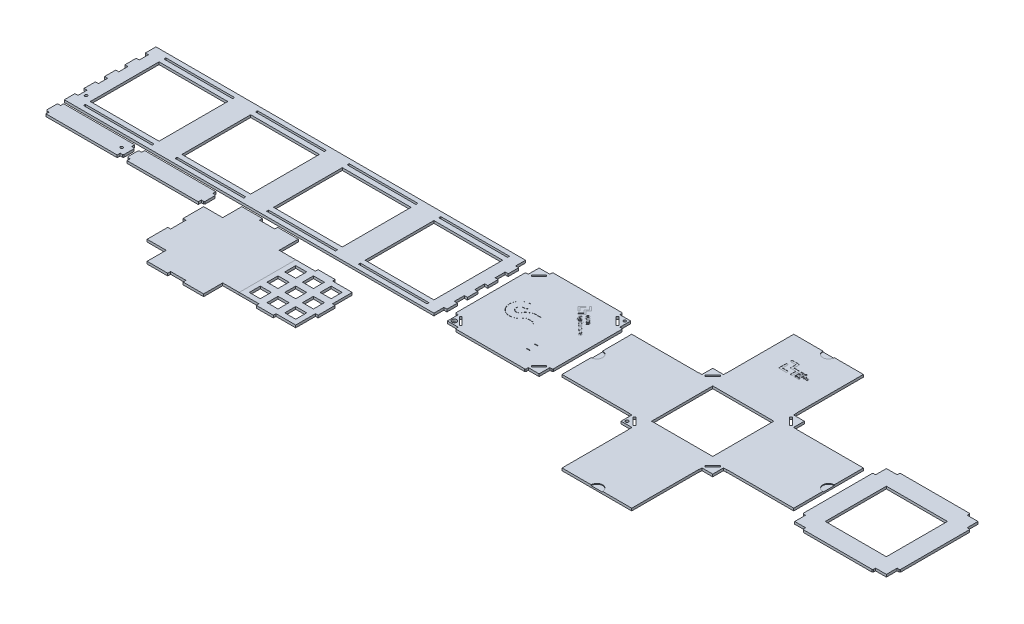
SolidWorks part; units mm, degrees
ref_plane "Front" through (0, 0, 0) normal (0, 0, 1) x (1, 0, 0)
ref_plane "Top" through (0, 0, 0) normal (0, 1, 0) x (1, 0, 0)
ref_plane "Right" through (0, 0, 0) normal (1, 0, 0) x (0, 0, -1)
sketch "Sketch1" plane through (0, 0, 0) normal (0, 1, 0) x (1, 0, 0)
  line L0 (0, 0) -> (228.6, 0) construction
  line L2 (-76.2, 76.2) -> (-76.2, -76.2) construction
  line L4 (76.2, 76.2) -> (76.2, -76.2) construction
  line L5 (-76.2, 76.2) -> (76.2, -76.2) construction
  line L6 (-76.2, -76.2) -> (76.2, 76.2) construction
  line L11 (76.2, 76.2) -> (228.6, 76.2)
  line L12 (76.2, 76.2) -> (76.2, -76.2) construction
  line L13 (76.2, -76.2) -> (228.6, -76.2)
  line L14 (228.6, 76.2) -> (228.6, -76.2) construction
  line L19 (-76.2, -76.2) -> (-228.6, -76.2)
  line L20 (-76.2, -76.2) -> (-76.2, 76.2) construction
  line L21 (-76.2, 76.2) -> (-228.6, 76.2)
  line L28 (76.2, -76.2) -> (-76.2, -76.2)
  line L34 (76.2, 76.2) -> (-76.2, 76.2)
  line L35 (-228.6, 76.2) -> (-228.6, -76.2) construction
  line L43 (-228.6, 76.2) -> (-381, 76.2)
  line L44 (-381, 76.2) -> (-381, -76.2) construction
  line L45 (-381, -76.2) -> (-228.6, -76.2)
  line L46 (228.6, 76.2) -> (228.6, 59.6392)
  line L47 (228.6, 59.6392) -> (233.68, 59.6392)
  line L48 (233.68, 59.6392) -> (233.68, 42.2402)
  line L49 (233.68, 42.2402) -> (228.6, 42.2402)
  line L50 (228.6, 42.2402) -> (228.6, 25.6794)
  line L51 (228.6, 25.6794) -> (233.68, 25.6794)
  line L63 (233.68, 25.6794) -> (233.68, 8.2804)
  line L64 (233.68, 8.2804) -> (228.6, 8.2804)
  line L65 (228.6, 8.2804) -> (228.6, -8.2804)
  line L66 (228.6, -8.2804) -> (233.68, -8.2804)
  line L67 (233.68, -8.2804) -> (233.68, -25.6794)
  line L68 (233.68, -25.6794) -> (228.6, -25.6794)
  line L69 (228.6, -25.6794) -> (228.6, -42.2402)
  line L70 (228.6, -42.2402) -> (233.68, -42.2402)
  line L71 (233.68, -42.2402) -> (233.68, -59.6392)
  line L72 (233.68, -59.6392) -> (228.6, -59.6392)
  line L73 (228.6, -59.6392) -> (228.6, -76.2)
  line L74 (-381, 76.2) -> (-386.08, 76.2)
  line L76 (-386.08, 58.5597) -> (-381, 58.5597)
  line L78 (-381, 43.3197) -> (-386.08, 43.3197)
  line L80 (-386.08, 24.5999) -> (-381, 24.5999)
  line L82 (-381, 9.3599) -> (-386.08, 9.3599)
  line L84 (-386.08, -9.3599) -> (-381, -9.3599)
  line L86 (-381, -24.5999) -> (-386.08, -24.5999)
  line L88 (-386.08, -43.3197) -> (-381, -43.3197)
  line L90 (-381, -58.5597) -> (-386.08, -58.5597)
  line L92 (-386.08, -76.2) -> (-381, -76.2)
  line L93 (233.68, 16.9799) -> (-381, 16.9799) construction
  line L94 (-381, 50.9397) -> (233.68, 50.9397) construction
  line L95 (-386.08, 76.2) -> (-386.08, 58.5597)
  line L96 (-386.08, 43.3197) -> (-386.08, 24.5999)
  line L97 (-381, 58.5597) -> (-381, 43.3197)
  line L98 (-381, 24.5999) -> (-381, 9.3599)
  line L99 (-381, -9.3599) -> (-381, -24.5999)
  line L100 (-381, -43.3197) -> (-381, -58.5597)
  line L101 (-381, -50.9397) -> (233.68, -50.9397) construction
  line L102 (-381, -16.9799) -> (233.68, -16.9799) construction
  line L103 (-386.08, 9.3599) -> (-386.08, -9.3599)
  line L104 (-386.08, -24.5999) -> (-386.08, -43.3197)
  line L105 (-386.08, -58.5597) -> (-386.08, -76.2)
  point P0 (0, 0)
  dimension "D1" = 152.4
  dimension "D3" = 5.08
  dimension "D5" = 15.24
  dimension "D4" = 17.399
  dimension "D2" = 152.4
extrude "Boss-Extrude1" add sketch "Sketch1" along normal blind 4.064
sketch "Sketch4" plane through (0, 4.064, 0) normal (0, 1, 0) x (1, 0, 0)
  line L0 (-228.6, 76.2) -> (-228.6, -76.2) construction
  line L1 (-228.6, 76.2) -> (-228.6, -76.2)
  line L2 (-76.2, 76.2) -> (-76.2, -76.2) construction
  line L3 (-76.2, 76.2) -> (-76.2, -76.2)
  line L4 (76.2, 76.2) -> (76.2, -76.2) construction
  line L5 (76.2, 76.2) -> (76.2, -76.2)
sketch "Sketch5" plane through (0, 4.064, 0) normal (0, 1, 0) x (1, 0, 0)
  line L0 (-381, -9.3599) -> (-381, 9.3599) construction
  line L1 (-228.6, 0) -> (-381, 0) construction
  line L2 (-228.6, 76.2) -> (-228.6, -76.2) construction
  line L3 (-228.6, 0) -> (-76.2, 0) construction
  line L4 (-76.2, 76.2) -> (-76.2, -76.2) construction
  line L5 (-76.2, 0) -> (76.2, 0) construction
  line L6 (76.2, 76.2) -> (76.2, -76.2) construction
  line L7 (76.2, 0) -> (228.6, 0) construction
  line L8 (228.6, -8.2804) -> (228.6, 8.2804) construction
  line L9 (-304.8, 0) -> (-304.8, -76.2) construction
  line L10 (-386.08, -76.2) -> (228.6, -76.2) construction
  line L11 (-152.4, 0) -> (-152.4, -76.2) construction
  line L12 (0, 0) -> (0, -76.2) construction
  line L13 (152.4, 0) -> (152.4, -76.2) construction
  line L14 (-247.65, -68.58) -> (-247.65, -76.2) construction
  line L15 (-361.95, -65.278) -> (-247.65, -65.278)
  line L16 (-361.95, -65.278) -> (-361.95, -68.58)
  line L17 (-361.95, -68.58) -> (-247.65, -68.58)
  line L18 (-247.65, -65.278) -> (-247.65, -68.58)
  line L19 (-361.95, -65.278) -> (-247.65, -68.58) construction
  line L20 (-361.95, -68.58) -> (-247.65, -65.278) construction
  line L21 (-209.55, -65.278) -> (-95.25, -65.278)
  line L22 (-209.55, -65.278) -> (-209.55, -68.58)
  line L23 (-209.55, -68.58) -> (-95.25, -68.58)
  line L24 (-95.25, -65.278) -> (-95.25, -68.58)
  line L25 (-209.55, -65.278) -> (-95.25, -68.58) construction
  line L26 (-209.55, -68.58) -> (-95.25, -65.278) construction
  line L27 (-57.15, -68.58) -> (57.15, -68.58)
  line L28 (-57.15, -68.58) -> (-57.15, -65.278)
  line L29 (-57.15, -65.278) -> (57.15, -65.278)
  line L30 (57.15, -68.58) -> (57.15, -65.278)
  line L31 (-57.15, -68.58) -> (57.15, -65.278) construction
  line L32 (-57.15, -65.278) -> (57.15, -68.58) construction
  line L33 (95.25, -68.58) -> (209.55, -68.58)
  line L34 (95.25, -68.58) -> (95.25, -65.278)
  line L35 (95.25, -65.278) -> (209.55, -65.278)
  line L36 (209.55, -68.58) -> (209.55, -65.278)
  line L37 (95.25, -68.58) -> (209.55, -65.278) construction
  line L38 (95.25, -65.278) -> (209.55, -68.58) construction
  line L39 (95.25, 65.278) -> (209.55, 68.58) construction
  line L40 (95.25, 68.58) -> (209.55, 65.278) construction
  line L41 (-57.15, 65.278) -> (57.15, 68.58) construction
  line L42 (-57.15, 68.58) -> (57.15, 65.278) construction
  line L43 (-209.55, 68.58) -> (-95.25, 65.278) construction
  line L44 (-209.55, 65.278) -> (-95.25, 68.58) construction
  line L45 (-361.95, 68.58) -> (-247.65, 65.278) construction
  line L46 (-361.95, 65.278) -> (-247.65, 68.58) construction
  line L47 (-247.65, 68.58) -> (-247.65, 76.2) construction
  line L48 (209.55, 68.58) -> (209.55, 65.278)
  line L49 (95.25, 65.278) -> (209.55, 65.278)
  line L50 (95.25, 68.58) -> (95.25, 65.278)
  line L51 (95.25, 68.58) -> (209.55, 68.58)
  line L52 (57.15, 68.58) -> (57.15, 65.278)
  line L53 (-57.15, 65.278) -> (57.15, 65.278)
  line L54 (-57.15, 68.58) -> (-57.15, 65.278)
  line L55 (-57.15, 68.58) -> (57.15, 68.58)
  line L56 (-95.25, 65.278) -> (-95.25, 68.58)
  line L57 (-209.55, 68.58) -> (-95.25, 68.58)
  line L58 (-209.55, 65.278) -> (-209.55, 68.58)
  line L59 (-209.55, 65.278) -> (-95.25, 65.278)
  line L60 (-247.65, 65.278) -> (-247.65, 68.58)
  line L61 (-361.95, 68.58) -> (-247.65, 68.58)
  line L62 (-361.95, 65.278) -> (-361.95, 68.58)
  line L63 (-361.95, 65.278) -> (-247.65, 65.278)
  line L65 (-361.95, 57.15) -> (-247.65, 57.15)
  line L66 (-361.95, 57.15) -> (-361.95, -57.15)
  line L67 (-361.95, -57.15) -> (-247.65, -57.15)
  line L68 (-247.65, 57.15) -> (-247.65, -57.15)
  line L69 (-361.95, 57.15) -> (-247.65, -57.15) construction
  line L70 (-361.95, -57.15) -> (-247.65, 57.15) construction
  line L71 (-209.55, 57.15) -> (-95.25, 57.15)
  line L72 (-209.55, 57.15) -> (-209.55, -57.15)
  line L73 (-209.55, -57.15) -> (-95.25, -57.15)
  line L74 (-95.25, 57.15) -> (-95.25, -57.15)
  line L75 (-209.55, 57.15) -> (-95.25, -57.15) construction
  line L76 (-209.55, -57.15) -> (-95.25, 57.15) construction
  line L77 (-57.15, 57.15) -> (57.15, 57.15)
  line L78 (-57.15, 57.15) -> (-57.15, -57.15)
  line L79 (-57.15, -57.15) -> (57.15, -57.15)
  line L80 (57.15, 57.15) -> (57.15, -57.15)
  line L81 (-57.15, 57.15) -> (57.15, -57.15) construction
  line L82 (-57.15, -57.15) -> (57.15, 57.15) construction
  line L83 (95.25, 57.15) -> (209.55, 57.15)
  line L84 (95.25, 57.15) -> (95.25, -57.15)
  line L85 (95.25, -57.15) -> (209.55, -57.15)
  line L86 (209.55, 57.15) -> (209.55, -57.15)
  line L87 (95.25, 57.15) -> (209.55, -57.15) construction
  line L88 (95.25, -57.15) -> (209.55, 57.15) construction
  circle A0 centre (-373.95, -52.15) radius 2.2225
  point P27 (-304.8, -66.929)
  point P32 (-152.4, -66.929)
  point P37 (0, -66.929)
  point P42 (152.4, -66.929)
  point P66 (152.4, 66.929)
  point P67 (0, 66.929)
  point P68 (-152.4, 66.929)
  point P69 (-304.8, 66.929)
  dimension "D5" = 4.445
  dimension "D1" = 7.62
  dimension "D3" = 114.3
  dimension "D6" = 12
  dimension "D7" = 5
  dimension "D8" = 19.05
  dimension "D2" = 3.302
  dimension "D4" = 8.128
extrude "Cut-Extrude2" cut sketch "Sketch5" against normal through all
sketch "Sketch6" plane through (0, 0, 0) normal (0, 1, 0) x (1, 0, 0)
  line L0 (0, 0) -> (327.279, 0) construction
  line L1 (327.279, 0) -> (327.279, 78.5495) construction
  line L2 (251.079, 76.2) -> (403.479, 76.2) construction
  line L3 (251.079, 76.2) -> (251.079, -76.2) construction
  line L4 (251.079, -76.2) -> (403.479, -76.2) construction
  line L5 (403.479, 76.2) -> (403.479, -76.2) construction
  line L6 (251.079, 76.2) -> (403.479, -76.2) construction
  line L7 (251.079, -76.2) -> (403.479, 76.2) construction
  line L8 (327.279, 0) -> (405.8285, 0) construction
  line L9 (327.279, 0) -> (327.279, -78.5495) construction
  line L10 (251.079, 58.2612) -> (251.079, 76.2)
  line L11 (269.0178, 80.899) -> (385.5403, 80.899)
  line L12 (269.0178, 80.899) -> (269.0178, 76.2)
  line L13 (269.0178, 76.2) -> (385.5403, 76.2) construction
  line L14 (385.5403, 80.899) -> (385.5403, 76.2)
  line L15 (269.0178, 80.899) -> (385.5403, 76.2) construction
  line L16 (269.0178, 76.2) -> (385.5403, 80.899) construction
  line L17 (408.178, -58.2612) -> (403.479, -58.2612)
  line L18 (408.178, -58.2612) -> (408.178, 58.2612)
  line L19 (408.178, 58.2612) -> (403.479, 58.2612)
  line L20 (403.479, -58.2612) -> (403.479, 58.2612) construction
  line L21 (408.178, -58.2612) -> (403.479, 58.2612) construction
  line L22 (408.178, 58.2612) -> (403.479, -58.2612) construction
  line L23 (269.0178, -80.899) -> (385.5403, -80.899)
  line L24 (269.0178, -80.899) -> (269.0178, -76.2)
  line L25 (269.0178, -76.2) -> (385.5403, -76.2) construction
  line L26 (385.5403, -80.899) -> (385.5403, -76.2)
  line L27 (269.0178, -80.899) -> (385.5403, -76.2) construction
  line L28 (269.0178, -76.2) -> (385.5403, -80.899) construction
  line L29 (246.38, 58.2612) -> (251.079, 58.2612)
  line L30 (246.38, 58.2612) -> (246.38, -58.2612)
  line L31 (246.38, -58.2612) -> (251.079, -58.2612)
  line L32 (251.079, 58.2612) -> (251.079, -58.2612) construction
  line L33 (246.38, 58.2612) -> (251.079, -58.2612) construction
  line L34 (246.38, -58.2612) -> (251.079, 58.2612) construction
  line L35 (251.079, 76.2) -> (269.0178, 76.2)
  line L36 (385.5403, 76.2) -> (403.479, 76.2)
  line L37 (403.479, 76.2) -> (403.479, 58.2612)
  line L38 (403.479, -58.2612) -> (403.479, -76.2)
  line L39 (403.479, -76.2) -> (385.5403, -76.2)
  line L40 (269.0178, -76.2) -> (251.079, -76.2)
  line L41 (251.079, -76.2) -> (251.079, -58.2612)
  line L42 (535.178, 58.2612) -> (535.178, -58.2612)
  line L43 (535.178, 58.2612) -> (539.877, 58.2612)
  line L44 (539.877, 58.2612) -> (539.877, 76.2)
  line L45 (539.877, 76.2) -> (557.8158, 76.2)
  line L46 (557.8158, 80.899) -> (557.8158, 76.2)
  line L47 (557.8158, 80.899) -> (674.3382, 80.899)
  line L48 (674.3382, 80.899) -> (674.3382, 76.2)
  line L49 (674.3382, 76.2) -> (692.277, 76.2)
  line L50 (692.277, 76.2) -> (692.277, 58.2612)
  line L51 (696.976, 58.2612) -> (692.277, 58.2612)
  line L52 (696.976, -58.2612) -> (696.976, 58.2612)
  line L53 (696.976, -58.2612) -> (692.277, -58.2612)
  line L54 (692.277, -58.2612) -> (692.277, -76.2)
  line L55 (692.277, -76.2) -> (674.3383, -76.2)
  line L56 (674.3383, -80.899) -> (674.3383, -76.2)
  line L57 (557.8158, -80.899) -> (674.3383, -80.899)
  line L58 (557.8158, -80.899) -> (557.8158, -76.2)
  line L59 (557.8158, -76.2) -> (539.877, -76.2)
  line L60 (539.877, -76.2) -> (539.877, -58.2612)
  line L61 (535.178, -58.2612) -> (539.877, -58.2612)
  line L62 (539.877, 76.2) -> (692.277, -76.2) construction
  line L63 (823.976, 58.2612) -> (823.976, -58.2612)
  line L64 (823.976, 58.2612) -> (828.675, 58.2612)
  line L65 (828.675, 58.2612) -> (828.675, 76.2)
  line L66 (828.675, 76.2) -> (846.6138, 76.2)
  line L67 (846.6138, 80.899) -> (846.6138, 76.2)
  line L68 (846.6138, 80.899) -> (963.1362, 80.899)
  line L69 (963.1362, 80.899) -> (963.1362, 76.2)
  line L70 (963.1362, 76.2) -> (981.075, 76.2)
  line L71 (981.075, 76.2) -> (981.075, 58.2612)
  line L72 (985.774, 58.2612) -> (981.075, 58.2612)
  line L73 (985.774, -58.2612) -> (985.774, 58.2612)
  line L74 (985.774, -58.2612) -> (981.075, -58.2612)
  line L75 (981.075, -58.2612) -> (981.075, -76.2)
  line L76 (981.075, -76.2) -> (963.1362, -76.2)
  line L77 (963.1362, -80.899) -> (963.1362, -76.2)
  line L78 (846.6138, -80.899) -> (963.1362, -80.899)
  line L79 (846.6138, -80.899) -> (846.6138, -76.2)
  line L80 (846.6138, -76.2) -> (828.675, -76.2)
  line L81 (828.675, -76.2) -> (828.675, -58.2612)
  line L82 (823.976, -58.2612) -> (828.675, -58.2612)
  line L83 (828.675, 76.2) -> (981.075, -76.2) construction
  line L84 (565.277, 50.8) -> (666.877, 50.8)
  line L85 (565.277, 50.8) -> (565.277, -50.8)
  line L86 (565.277, -50.8) -> (666.877, -50.8)
  line L87 (666.877, 50.8) -> (666.877, -50.8)
  line L88 (565.277, 50.8) -> (666.877, -50.8) construction
  line L89 (565.277, -50.8) -> (666.877, 50.8) construction
  line L90 (233.68, -25.6794) -> (233.68, -8.2804) construction
  line L91 (955.675, 50.8) -> (854.075, 50.8)
  line L92 (955.675, 50.8) -> (955.675, -50.8)
  line L93 (955.675, -50.8) -> (854.075, -50.8)
  line L94 (854.075, 50.8) -> (854.075, -50.8)
  line L95 (955.675, 50.8) -> (854.075, -50.8) construction
  line L96 (955.675, -50.8) -> (854.075, 50.8) construction
  line L97 (-76.2, -57.15) -> (76.2, -57.15) construction
  line L98 (-76.2, 76.2) -> (-76.2, -76.2) construction
  line L99 (76.2, 76.2) -> (76.2, -76.2) construction
  line L100 (76.2, -57.15) -> (228.6, -57.15) construction
  line L101 (228.6, -76.2) -> (228.6, -59.6392) construction
  line L102 (-57.15, -57.15) -> (57.15, -57.15) construction
  line L103 (95.25, 57.15) -> (209.55, 57.15) construction
  point P22 (248.7295, 0)
  point P67 (616.077, 0)
  point P72 (904.875, 0)
  dimension "D8" = 101.6
  dimension "D5" = 12.7
  dimension "D1" = 114.3
  dimension "D2" = 116.5225
  dimension "D4" = 127
  dimension "D3" = 4.699
  dimension "D6" = 3
extrude "Boss-Extrude2" add sketch "Sketch6" along normal up to surface (4.064 mm away) separate body up to face at (-152.4, 4.064, 0)
sketch "Sketch7" plane through (0, 0, 0) normal (0, 1, 0) x (1, 0, 0)
  line L0 (-361.95, 65.278) -> (-361.95, -53.086) construction
  line L1 (-381, -82.55) -> (-262.636, -82.55)
  line L2 (-381, -82.55) -> (-381, -87.63)
  line L3 (-381, -111.76) -> (-262.636, -111.76)
  line L4 (-262.636, -82.55) -> (-262.636, -87.63)
  line L5 (-381, -82.55) -> (-262.636, -111.76) construction
  line L6 (-381, -111.76) -> (-262.636, -82.55) construction
  line L7 (-361.95, 57.15) -> (-361.95, -57.15) construction
  line L8 (-361.95, -53.086) -> (-361.95, -57.15) construction
  line L9 (251.079, -58.2612) -> (251.079, -76.2) construction
  line L10 (251.079, -76.2) -> (269.0178, -76.2) construction
  line L12 (-381, -87.63) -> (-386.08, -87.63)
  line L13 (256.9951, -57.7116) -> (269.5674, -70.2839) construction
  line L14 (256.9951, -57.7116) -> (254.6602, -60.0464) construction
  line L15 (254.6602, -60.0464) -> (267.2326, -72.6188) construction
  line L16 (269.5674, -70.2839) -> (267.2326, -72.6188) construction
  line L17 (256.9951, -57.7116) -> (267.2326, -72.6188) construction
  line L18 (254.6602, -60.0464) -> (269.5674, -70.2839) construction
  line L19 (-386.08, -87.63) -> (-386.08, -106.68)
  line L20 (-386.08, -106.68) -> (-381, -106.68)
  line L22 (262.1138, -65.1652) -> (260.0484, -67.2306) construction
  line L23 (-381, -106.68) -> (-381, -111.76)
  line L24 (-262.636, -87.63) -> (-257.556, -87.63)
  line L25 (-257.556, -87.63) -> (-257.556, -106.68)
  line L26 (-257.556, -106.68) -> (-262.636, -106.68)
  line L27 (-262.636, -106.68) -> (-262.636, -111.76)
  line L28 (-386.08, -76.2) -> (228.6, -76.2) construction
  line L29 (-386.08, -58.5597) -> (-386.08, -76.2) construction
  line L30 (-246.126, -82.55) -> (-127.762, -82.55)
  line L31 (-246.126, -82.55) -> (-246.126, -87.63)
  line L32 (-246.126, -111.76) -> (-127.762, -111.76)
  line L33 (-127.762, -82.55) -> (-127.762, -87.63)
  line L34 (-246.126, -87.63) -> (-251.206, -87.63)
  line L35 (-251.206, -87.63) -> (-251.206, -106.68)
  line L36 (-251.206, -106.68) -> (-246.126, -106.68)
  line L37 (-246.126, -106.68) -> (-246.126, -111.76)
  line L38 (-127.762, -87.63) -> (-122.682, -87.63)
  line L39 (-122.682, -87.63) -> (-122.682, -106.68)
  line L40 (-122.682, -106.68) -> (-127.762, -106.68)
  line L41 (-127.762, -106.68) -> (-127.762, -111.76)
  line L42 (-246.126, -82.55) -> (-127.762, -111.76) construction
  line L43 (-246.126, -111.76) -> (-127.762, -82.55) construction
  line L44 (-361.95, 65.278) -> (-386.08, 65.278) construction
  line L45 (-386.08, 76.2) -> (-386.08, 58.5597) construction
  line L46 (251.079, -58.2612) -> (269.0178, -76.2) construction
  point P0 (-321.818, -97.155)
  point P14 (262.1138, -65.1652)
  point P38 (-186.944, -97.155)
  dimension "D1" = 29.21
  dimension "D4" = 19.05
  dimension "D5" = 17.78
  dimension "D7" = 6.35
  dimension "D9" = 6.35
  dimension "D10" = 1.27
  dimension "D3" = 3.302
  dimension "D6" = 5.08
  dimension "D2" = 4.064
extrude "PILLAR POSITION" add sketch "Sketch7" along normal up to surface (4.064 mm away) separate body up to face at (-152.4, 4.064, 0)
sketch "Sketch8" plane through (0, 4.064, 0) normal (0, 1, 0) x (1, 0, 0)
  line L0 (254.6602, -60.0464) -> (267.2326, -72.6188) construction
  line L1 (269.5674, -70.2839) -> (267.2326, -72.6188) construction
  line L2 (256.9951, -57.7116) -> (269.5674, -70.2839) construction
  line L3 (256.9951, -57.7116) -> (254.6602, -60.0464) construction
  line L4 (254.6602, -60.0464) -> (267.2326, -72.6188)
  line L5 (269.5674, -70.2839) -> (267.2326, -72.6188)
  line L6 (256.9951, -57.7116) -> (269.5674, -70.2839)
  line L7 (256.9951, -57.7116) -> (254.6602, -60.0464)
  line L8 (251.079, 76.2) -> (403.479, -76.2) construction
  line L9 (269.5674, 70.2839) -> (256.9951, 57.7116)
  line L10 (269.5674, 70.2839) -> (267.2326, 72.6188)
  line L11 (267.2326, 72.6188) -> (254.6602, 60.0464)
  line L12 (256.9951, 57.7116) -> (254.6602, 60.0464)
  line L13 (397.5629, 57.7116) -> (384.9906, 70.2839)
  line L14 (397.5629, 57.7116) -> (399.8978, 60.0464)
  line L15 (399.8978, 60.0464) -> (387.3254, 72.6188)
  line L16 (384.9906, 70.2839) -> (387.3254, 72.6188)
  line L17 (384.9906, -70.2839) -> (397.5629, -57.7116)
  line L18 (384.9906, -70.2839) -> (387.3254, -72.6188)
  line L19 (387.3254, -72.6188) -> (399.8978, -60.0464)
  line L20 (397.5629, -57.7116) -> (399.8978, -60.0464)
  line L21 (539.877, -58.2612) -> (557.8158, -76.2) construction
  line L22 (543.4582, -60.0464) -> (545.7931, -57.7116)
  line L23 (545.7931, -57.7116) -> (558.3654, -70.2839)
  line L24 (558.3654, -70.2839) -> (556.0306, -72.6188)
  line L25 (548.8464, -67.2306) -> (552.0793, -63.9977) construction
  line L26 (543.4582, -60.0464) -> (556.0306, -72.6188)
  line L27 (539.877, 76.2) -> (692.277, -76.2) construction
  line L28 (545.7931, 57.7116) -> (543.4582, 60.0464)
  line L29 (556.0306, 72.6188) -> (543.4582, 60.0464)
  line L30 (556.0306, 72.6188) -> (558.3654, 70.2839)
  line L31 (558.3654, 70.2839) -> (545.7931, 57.7116)
  line L32 (673.7886, 70.2839) -> (676.1234, 72.6188)
  line L33 (688.6958, 60.0464) -> (676.1234, 72.6188)
  line L34 (688.6958, 60.0464) -> (686.3609, 57.7116)
  line L35 (686.3609, 57.7116) -> (673.7886, 70.2839)
  line L36 (686.3609, -57.7116) -> (688.6958, -60.0464)
  line L37 (676.1234, -72.6188) -> (688.6958, -60.0464)
  line L38 (676.1234, -72.6188) -> (673.7886, -70.2839)
  line L39 (673.7886, -70.2839) -> (686.3609, -57.7116)
  line L40 (251.079, -58.2612) -> (269.0178, -76.2) construction
  line L41 (260.9464, -66.3326) -> (260.0484, -67.2306) construction
  line L42 (556.0306, -72.6188) -> (555.1326, -73.5168) construction
  circle A0 centre (327.279, 0) radius 20.7898 construction
  circle A1 centre (327.279, 0) radius 20.7898 construction
  circle A2 centre (327.279, 0) radius 20.7898 construction
  circle A3 centre (327.279, 0) radius 20.7898 construction
  circle A4 centre (616.077, 0) radius 71.842 construction
  point P28 (327.279, 0)
  point P58 (616.077, 0)
  dimension "D3" = 41.5796
  dimension "D1" = 4
  dimension "D2" = 4
extrude "Cut-Extrude3" cut sketch "Sketch8" against normal through all
sketch "Sketch10" plane through (0, 4.064, 0) normal (0, 1, 0) x (1, 0, 0)
  line L8 (-361.95, -53.086) -> (-247.65, -53.086)
  line L9 (-304.8, -53.086) -> (-304.8, -57.15) construction
  line L14 (-361.95, 57.15) -> (-361.95, -57.15) construction
  line L15 (-247.65, -57.15) -> (-247.65, 57.15) construction
  line L16 (-361.95, -57.15) -> (-247.65, -57.15) construction
  line L17 (-209.55, -53.086) -> (-95.25, -53.086)
  line L18 (-209.55, 57.15) -> (-209.55, -57.15) construction
  line L19 (-95.25, -57.15) -> (-95.25, 57.15) construction
  line L20 (-57.15, -53.086) -> (57.15, -53.086)
  line L21 (-57.15, 57.15) -> (-57.15, -57.15) construction
  line L22 (57.15, -57.15) -> (57.15, 57.15) construction
  line L23 (95.25, -53.086) -> (209.55, -53.086)
  line L24 (95.25, 57.15) -> (95.25, -57.15) construction
  line L25 (209.55, -57.15) -> (209.55, 57.15) construction
  line L27 (-361.95, 57.15) -> (-361.95, -53.086) construction
  dimension "D1" = 4.064
sketch "Sketch11" plane through (0, 0, 0) normal (0, 1, 0) x (1, 0, 0)
  line L0 (-209.55, -57.15) -> (-209.55, -65.278) construction
  line L5 (-84.582, -114.3) -> (9.398, -114.3) construction
  line L6 (-84.582, -114.3) -> (-84.582, -208.28) construction
  line L7 (-84.582, -208.28) -> (9.398, -208.28) construction
  line L8 (9.398, -114.3) -> (9.398, -208.28) construction
  line L9 (-84.582, -114.3) -> (9.398, -208.28) construction
  line L10 (-84.582, -208.28) -> (9.398, -114.3) construction
  line L11 (-84.582, -114.3) -> (-116.332, -114.3)
  line L12 (-116.332, -114.3) -> (-116.332, -208.28)
  line L13 (-116.332, -208.28) -> (-84.582, -208.28)
  line L14 (-84.582, -114.3) -> (-84.582, -82.55)
  line L15 (-84.582, -82.55) -> (9.398, -82.55)
  line L16 (9.398, -82.55) -> (9.398, -114.3)
  line L17 (9.398, -114.3) -> (36.83, -114.3)
  line L18 (36.83, -114.3) -> (36.83, -208.28)
  line L19 (36.83, -208.28) -> (9.398, -208.28)
  line L20 (9.398, -208.28) -> (9.398, -240.03)
  line L21 (9.398, -240.03) -> (-84.582, -240.03)
  line L22 (-84.582, -240.03) -> (-84.582, -208.28)
  line L23 (-386.08, -76.2) -> (228.6, -76.2) construction
  line L24 (-122.682, -106.68) -> (-122.682, -87.63) construction
  line L25 (-209.55, -57.15) -> (-95.25, -57.15) construction
  line L26 (565.277, -50.8) -> (666.877, -50.8) construction
  line L27 (209.55, -53.086) -> (209.55, -76.2) construction
  line L28 (-88.646, -237.49) -> (13.462, -237.49) construction
  line L29 (-37.592, -161.29) -> (-37.592, -237.49) construction
  line L30 (-88.646, -237.49) -> (-88.646, -240.03) construction
  line L31 (-88.646, -240.03) -> (-84.582, -240.03) construction
  line L32 (9.398, -240.03) -> (13.462, -240.03) construction
  line L33 (13.462, -240.03) -> (13.462, -237.49) construction
  point P0 (-37.592, -161.29)
  point P33 (-37.592, -237.49)
  dimension "D1" = 4.064
  dimension "D2" = 101.6
  dimension "D3" = 102.108
  dimension "D4" = 6.35
  dimension "D5" = 6.35
  dimension "D6" = 2.54
  dimension "D7" = 31.75
  dimension "D8" = 27.432
extrude "Boss-Extrude5" add sketch "Sketch11" along normal up to surface (4.064 mm away) separate body up to face at (-152.4, 4.064, 0)
sketch "Sketch12" plane through (0, 4.064, 0) normal (0, 1, 0) x (1, 0, 0)
  line L0 (-84.582, -114.3) -> (9.398, -114.3)
  line L1 (9.398, -114.3) -> (9.398, -208.28)
  line L2 (9.398, -208.28) -> (-84.582, -208.28)
  line L3 (-84.582, -114.3) -> (-84.582, -208.28)
sketch "Sketch14" plane through (0, 4.064, 0) normal (0, 1, 0) x (1, 0, 0)
  line L0 (-257.556, -97.155) -> (-269.7785, -97.155) construction
  line L1 (-257.556, -106.68) -> (-257.556, -87.63) construction
  circle A0 centre (-269.7785, -97.155) radius 2.2225
  circle A1 centre (-373.95, -52.15) radius 2.2225 construction
  dimension "D1" = 10
extrude "Cut-Extrude4" cut sketch "Sketch14" against normal through all
sketch "Sketch15" plane through (0, 4.064, 0) normal (0, 1, 0) x (1, 0, 0)
  line L0 (251.079, -76.2) -> (260.9464, -66.3326) construction
  line L1 (254.6602, -60.0464) -> (267.2326, -72.6188) construction
  line L2 (256.8592, -76.5158) -> (256.8592, -76.2) construction
  line L3 (251.079, -76.2) -> (269.0178, -76.2) construction
  line L4 (260.9464, -66.3326) -> (261.1697, -66.1093) construction
  line L5 (251.079, 76.2) -> (403.479, -76.2) construction
  line L6 (403.479, 76.2) -> (393.6116, 66.3326) construction
  line L7 (399.8978, 60.0464) -> (387.3254, 72.6188) construction
  line L8 (549.7444, -66.3326) -> (539.877, -76.2) construction
  line L9 (543.4582, -60.0464) -> (556.0306, -72.6188) construction
  circle A0 centre (256.8592, -70.4198) radius 3.95
  circle A1 centre (256.8592, -70.4198) radius 6.096 construction
  circle A2 centre (398.5453, 71.2663) radius 2.2225
  circle A3 centre (-269.7785, -97.155) radius 2.2225 construction
  circle A4 centre (544.8107, -71.2663) radius 2.413
  dimension "D1" = 7.9
  dimension "D2" = 12.192
  dimension "D3" = 4.826
extrude "Cut-Extrude5" cut sketch "Sketch15" against normal through all
sketch "Sketch16" [suppressed] plane through (0, 4.064, 0) normal (0, 1, 0) x (1, 0, 0)
  line L0 (565.277, 50.8) -> (565.277, -50.8) construction
  line L1 (568.452, 19.05) -> (481.6251, 19.05) construction
  line L2 (568.452, 38.1) -> (606.552, 38.1)
  line L3 (568.452, 38.1) -> (568.452, 0)
  line L4 (568.452, 0) -> (606.552, 0)
  line L6 (568.452, 38.1) -> (606.552, 0) construction
  line L7 (568.452, 0) -> (606.552, 38.1) construction
  line L8 (481.6251, 19.05) -> (587.502, 19.05) construction
  line L9 (606.552, 38.1) -> (606.552, 21.4244)
  line L10 (610.9668, 24.6016) -> (610.8822, 24.7481)
  line L11 (587.502, 38.1) -> (587.502, 0) construction
  line L12 (600.202, 24.13) -> (590.804, 24.13)
  line L13 (600.202, 13.97) -> (590.804, 13.97)
  line L14 (587.502, 24.13) -> (587.502, 13.97) construction
  line L15 (610.616, 24.13) -> (587.502, 24.13) construction
  line L16 (610.616, 13.97) -> (587.502, 13.97) construction
  line L17 (603.4053, 23.2628) -> (608.0662, 20.5397)
  line L18 (610.616, 19.05) -> (609.8932, 19.05) construction
  line L19 (610.616, 19.05) -> (587.502, 19.05) construction
  line L20 (625.8721, 19.05) -> (609.8932, 19.05) construction
  line L21 (600.202, 24.13) -> (600.202, 13.97) construction
  line L22 (606.552, -9.6369) -> (606.552, 0)
  line L23 (666.877, 50.8) -> (565.277, 50.8) construction
  line L24 (587.502, 27.432) -> (587.502, 27.94) construction
  line L25 (587.502, 10.668) -> (587.502, 10.16) construction
  line L26 (587.502, 27.432) -> (587.502, 10.668)
  arc A1 (611.0062, 17.4306) -> (614.2938, 22.6039) centre (614.172, 19.05) ccw
  arc A3 (614.4368, 30.7471) -> (610.8822, 24.7481) centre (614.3463, 26.7481) ccw
  arc A4 (610.9668, 24.6016) -> (614.2938, 22.6039) centre (614.4309, 26.6016) ccw
  arc A5 (603.4053, 23.2628) -> (600.202, 24.13) centre (600.202, 17.78) ccw
  arc A6 (605.1166, 11.6411) -> (600.202, 13.97) centre (600.202, 7.62) ccw
  arc A7 (611.0062, 17.4306) -> (608.0662, 20.5397) centre (604.2222, 13.9603) ccw
  arc A8 (590.804, 13.97) -> (587.502, 10.668) centre (590.804, 10.668) ccw
  arc A9 (587.502, 27.432) -> (590.804, 24.13) centre (590.804, 27.432) ccw
  arc A10 (605.1166, 11.6411) -> (614.4368, 30.7471) centre (614.172, 19.05) ccw
  point P4 (587.502, 19.05)
  point P28 (371.8905, 14.7821)
  dimension "D7" = 4
  dimension "D8" = 6.35
  dimension "D9" = 6.35
  dimension "D10" = 7.62
  dimension "D12" = 7.112
  dimension "D17" = 3.302
  dimension "D1" = 38.1
  dimension "D2" = 38.1
  dimension "D3" = 12.7
  dimension "D4" = 5.08
  dimension "D6" = 30
  dimension "D11" = 26.67
  dimension "D13" = 3.175
  dimension "D14" = 12.7
  dimension "D15" = 3.81
  dimension "D16" = 3.81
  dimension "D5" = 5.08
sketch "Sketch17" plane through (0, 4.064, 0) normal (0, 1, 0) x (1, 0, 0)
  line L1 (327.279, 80.899) -> (327.279, -80.899) construction
  line L12 (385.5403, 80.899) -> (269.0178, 80.899) construction
  line L13 (269.0178, -80.899) -> (385.5403, -80.899) construction
  line L30 (327.279, 10.16) -> (327.279, -10.16) construction
  line L31 (295.529, 0) -> (359.029, 0) construction
  line L32 (304.967, 2.1893) -> (310.047, 5.1321)
  line L34 (322.3603, -6.35) -> (314.579, -6.35)
  line L35 (314.579, 6.35) -> (322.3603, 6.35)
  arc A9 (310.047, 5.1321) -> (314.579, 6.35) centre (314.579, -2.6913) cw
  arc A10 (301.5552, -2.0019) -> (304.967, 2.1893) centre (308.7866, -4.4043) cw
  arc A11 (301.5552, -2.0019) -> (295.7963, 6.3444) centre (295.529, 0) cw
  arc A14 (310.4346, -8.7261) -> (296.256, 17.2567) centre (295.529, 0) cw
  arc A15 (310.4346, -8.7261) -> (314.579, -6.35) centre (314.579, -11.1524) cw
  arc A16 (322.3603, -6.35) -> (327.279, -10.16) centre (322.3603, -11.43) cw
  arc A17 (327.279, 10.16) -> (322.3603, 6.35) centre (322.3603, 11.43) cw
  arc A36 (296.256, 17.2567) -> (295.7963, 6.3444) centre (296.0261, 11.8005) cw
  point P43 (327.279, 0)
  point P64 (327.279, 0)
  dimension "D4" = 17.272
  dimension "D5" = 12.7
  dimension "D6" = 5.08
  dimension "D2" = 31.75
  dimension "D3" = 6.35
  dimension "D8" = 0.4971
  dimension "D9" = 7.62
  dimension "D7" = 20.32
  dimension "D10" = 5.08
  dimension "D11" = 12.7
  dimension "D12" = 30.084
extrude "Cut-Extrude-Thin1" cut sketch "Sketch17" against normal through all thin contours A16 L34 A15 A14 A36 A11 A10 L32 A9 L35 A17 thin type one direction wall 0.25
sketch "Sketch19" plane through (0, 4.064, 0) normal (0, 1, 0) x (1, 0, 0)
  line L0 (36.83, -114.3) -> (130.81, -208.28) construction
  line L1 (36.83, -114.3) -> (130.81, -114.3)
  line L2 (36.83, -114.3) -> (36.83, -208.28)
  line L3 (36.83, -208.28) -> (130.81, -208.28)
  line L4 (130.81, -114.3) -> (130.81, -208.28)
  line L6 (54.356, -131.826) -> (113.284, -131.826) construction
  line L7 (54.356, -131.826) -> (54.356, -190.754) construction
  line L8 (54.356, -190.754) -> (113.284, -190.754) construction
  line L9 (113.284, -131.826) -> (113.284, -190.754) construction
  line L10 (54.356, -131.826) -> (113.284, -190.754) construction
  line L11 (54.356, -190.754) -> (113.284, -131.826) construction
  line L12 (36.83, -114.3) -> (36.83, -208.28) construction
  line L13 (36.83, -114.3) -> (9.398, -114.3) construction
  line L14 (74.676, -122.682) -> (92.964, -122.682)
  line L15 (104.14, -122.682) -> (122.428, -122.682)
  line L16 (104.14, -122.682) -> (104.14, -140.97)
  line L17 (104.14, -140.97) -> (122.428, -140.97)
  line L18 (122.428, -122.682) -> (122.428, -140.97)
  line L19 (104.14, -122.682) -> (122.428, -140.97) construction
  line L20 (104.14, -140.97) -> (122.428, -122.682) construction
  line L21 (63.5, -122.682) -> (45.212, -122.682)
  line L22 (63.5, -122.682) -> (63.5, -140.97)
  line L23 (63.5, -140.97) -> (45.212, -140.97)
  line L24 (45.212, -122.682) -> (45.212, -140.97)
  line L25 (63.5, -122.682) -> (45.212, -140.97) construction
  line L26 (63.5, -140.97) -> (45.212, -122.682) construction
  line L27 (45.212, -181.61) -> (63.5, -181.61)
  line L28 (45.212, -181.61) -> (45.212, -199.898)
  line L29 (45.212, -199.898) -> (63.5, -199.898)
  line L30 (63.5, -181.61) -> (63.5, -199.898)
  line L31 (45.212, -181.61) -> (63.5, -199.898) construction
  line L32 (45.212, -199.898) -> (63.5, -181.61) construction
  line L33 (104.14, -181.61) -> (122.428, -181.61)
  line L34 (104.14, -181.61) -> (104.14, -199.898)
  line L35 (104.14, -199.898) -> (122.428, -199.898)
  line L36 (122.428, -181.61) -> (122.428, -199.898)
  line L37 (104.14, -181.61) -> (122.428, -199.898) construction
  line L38 (104.14, -199.898) -> (122.428, -181.61) construction
  line L39 (74.676, -122.682) -> (74.676, -140.97)
  line L40 (74.676, -140.97) -> (92.964, -140.97)
  line L41 (92.964, -122.682) -> (92.964, -140.97)
  line L42 (74.676, -122.682) -> (92.964, -140.97) construction
  line L43 (74.676, -140.97) -> (92.964, -122.682) construction
  line L44 (45.212, -152.146) -> (63.5, -152.146)
  line L45 (45.212, -152.146) -> (45.212, -170.434)
  line L46 (45.212, -170.434) -> (63.5, -170.434)
  line L47 (63.5, -152.146) -> (63.5, -170.434)
  line L48 (45.212, -152.146) -> (63.5, -170.434) construction
  line L49 (45.212, -170.434) -> (63.5, -152.146) construction
  line L50 (74.676, -181.61) -> (92.964, -181.61)
  line L51 (74.676, -181.61) -> (74.676, -199.898)
  line L52 (74.676, -199.898) -> (92.964, -199.898)
  line L53 (92.964, -181.61) -> (92.964, -199.898)
  line L54 (74.676, -181.61) -> (92.964, -199.898) construction
  line L55 (74.676, -199.898) -> (92.964, -181.61) construction
  line L56 (104.14, -152.146) -> (122.428, -152.146)
  line L57 (104.14, -152.146) -> (104.14, -170.434)
  line L58 (104.14, -170.434) -> (122.428, -170.434)
  line L59 (122.428, -152.146) -> (122.428, -170.434)
  line L60 (104.14, -152.146) -> (122.428, -170.434) construction
  line L61 (104.14, -170.434) -> (122.428, -152.146) construction
  line L62 (74.676, -152.146) -> (92.964, -152.146)
  line L63 (74.676, -152.146) -> (74.676, -170.434)
  line L64 (74.676, -170.434) -> (92.964, -170.434)
  line L65 (92.964, -152.146) -> (92.964, -170.434)
  line L66 (74.676, -152.146) -> (92.964, -170.434) construction
  line L67 (74.676, -170.434) -> (92.964, -152.146) construction
  point P4 (83.82, -161.29)
  point P31 (83.82, -131.826)
  point P36 (54.356, -161.29)
  point P41 (83.82, -190.754)
  point P46 (113.284, -161.29)
  point P51 (83.82, -161.29)
  point P58 (130.81, -114.3)
  dimension "D4" = 18.288
  dimension "D5" = 40.64
  dimension "D6" = 8.382
extrude "Boss-Extrude9" add sketch "Sketch19" against normal up to surface (4.064 mm away) separate body up to face at (-38.3117, 0, 161.29)
chamfer "Chamfer1" distance 1.27 angle 45 8 edges at (246.38, 2.032, -58.2612) (246.38, 2.032, 58.2612) (269.0178, 2.032, 80.899) (385.5403, 2.032, 80.899) (408.178, 2.032, 58.2612) (408.178, 2.032, -58.2612) (385.5403, 2.032, -80.899) (269.0178, 2.032, -80.899)
chamfer "Chamfer3" distance 1.25 angle 45 8 edges at (985.774, 2.032, -58.2612) (985.774, 2.032, 58.2612) (963.1362, 2.032, 80.899) (846.6138, 2.032, 80.899) (823.976, 2.032, 58.2612) (963.1362, 2.032, -80.899) (823.976, 2.032, -58.2612) (846.6138, 2.032, -80.899)
chamfer "Chamfer4" distance 1.25 angle 45 4 edges at (-257.556, 2.032, 106.68) (-257.556, 2.032, 87.63) (-386.08, 2.032, 106.68) (-386.08, 2.032, 87.63)
chamfer "Chamfer5" distance 1.25 angle 45 4 edges at (-122.682, 2.032, 87.63) (-122.682, 2.032, 106.68) (-251.206, 2.032, 106.68) (-251.206, 2.032, 87.63)
sketch "Sketch20" plane through (0, 4.064, 0) normal (0, 1, 0) x (1, 0, 0)
  line L0 (359.664, -36.83) -> (359.664, -50.038) construction
  line L1 (356.87, -36.449) -> (362.458, -36.449)
  line L2 (356.87, -36.449) -> (356.87, -37.211)
  line L3 (356.87, -37.211) -> (362.458, -37.211)
  line L4 (362.458, -36.449) -> (362.458, -37.211)
  line L5 (356.87, -36.449) -> (362.458, -37.211) construction
  line L6 (356.87, -37.211) -> (362.458, -36.449) construction
  line L7 (356.87, -49.657) -> (362.458, -49.657)
  line L8 (356.87, -49.657) -> (356.87, -50.419)
  line L9 (356.87, -50.419) -> (362.458, -50.419)
  line L10 (362.458, -49.657) -> (362.458, -50.419)
  line L11 (356.87, -49.657) -> (362.458, -50.419) construction
  line L12 (356.87, -50.419) -> (362.458, -49.657) construction
  line L13 (270.2878, -80.899) -> (384.2703, -80.899) construction
  line L14 (408.178, -56.9912) -> (408.178, 56.9912) construction
  point P0 (359.664, -36.83)
  point P5 (359.664, -50.038)
  dimension "D1" = 0.762
  dimension "D2" = 5.588
  dimension "D3" = 13.97
  dimension "D4" = 30.48
  dimension "D5" = 45.72
extrude "Cut-Extrude7" cut sketch "Sketch20" against normal through all
sketch "Sketch21" plane through (0, 4.064, 0) normal (0, 1, 0) x (1, 0, 0)
  line L0 (-37.592, -82.55) -> (-37.592, -240.03) construction
  line L1 (9.398, -82.55) -> (-84.582, -82.55) construction
  line L2 (-84.582, -240.03) -> (9.398, -240.03) construction
  line L3 (-116.332, -161.29) -> (36.83, -161.29) construction
  line L4 (-116.332, -114.3) -> (-116.332, -208.28) construction
  line L5 (36.83, -114.3) -> (36.83, -208.28) construction
  line L7 (-50.292, -82.55) -> (-24.892, -82.55)
  line L8 (-50.292, -82.55) -> (-50.292, -87.376)
  line L9 (-50.292, -87.376) -> (-24.892, -87.376)
  line L10 (-24.892, -82.55) -> (-24.892, -87.376)
  line L11 (-50.292, -82.55) -> (-24.892, -87.376) construction
  line L12 (-50.292, -87.376) -> (-24.892, -82.55) construction
  line L13 (-116.332, -148.59) -> (-111.506, -148.59)
  line L14 (-116.332, -148.59) -> (-116.332, -173.99)
  line L15 (-116.332, -173.99) -> (-111.506, -173.99)
  line L16 (-111.506, -148.59) -> (-111.506, -173.99)
  line L17 (-116.332, -148.59) -> (-111.506, -173.99) construction
  line L18 (-116.332, -173.99) -> (-111.506, -148.59) construction
  line L19 (-50.292, -235.204) -> (-24.892, -235.204)
  line L20 (-50.292, -235.204) -> (-50.292, -240.03)
  line L21 (-50.292, -240.03) -> (-24.892, -240.03)
  line L22 (-24.892, -235.204) -> (-24.892, -240.03)
  line L23 (-50.292, -235.204) -> (-24.892, -240.03) construction
  line L24 (-50.292, -240.03) -> (-24.892, -235.204) construction
  point P12 (-37.592, -84.963)
  point P17 (-113.919, -161.29)
  point P22 (-37.592, -237.617)
  dimension "D1" = 25.4
  dimension "D2" = 4.826
extrude "Cut-Extrude8" cut sketch "Sketch21" against normal through all
sketch "Sketch22" plane through (0, 0, 0) normal (0, -1, 0) x (-1, 0, 0)
  line L0 (-83.82, -114.3) -> (-83.82, -208.28) construction
  line L1 (-130.81, -114.3) -> (-36.83, -114.3) construction
  line L2 (-36.83, -208.28) -> (-130.81, -208.28) construction
  line L3 (-130.81, -161.29) -> (-83.82, -161.29) construction
  line L4 (-130.81, -208.28) -> (-130.81, -114.3) construction
  line L5 (-130.81, -114.3) -> (-36.83, -114.3) construction
  line L6 (-97.9805, -109.855) -> (-69.6595, -109.855)
  line L7 (-97.9805, -109.855) -> (-97.9805, -118.745)
  line L8 (-97.9805, -118.745) -> (-69.6595, -118.745)
  line L9 (-69.6595, -109.855) -> (-69.6595, -118.745)
  line L10 (-97.9805, -109.855) -> (-69.6595, -118.745) construction
  line L11 (-97.9805, -118.745) -> (-69.6595, -109.855) construction
  line L12 (-135.255, -147.1295) -> (-126.365, -147.1295)
  line L13 (-135.255, -147.1295) -> (-135.255, -175.4505)
  line L14 (-135.255, -175.4505) -> (-126.365, -175.4505)
  line L15 (-126.365, -147.1295) -> (-126.365, -175.4505)
  line L16 (-135.255, -147.1295) -> (-126.365, -175.4505) construction
  line L17 (-135.255, -175.4505) -> (-126.365, -147.1295) construction
  line L18 (-97.9805, -203.835) -> (-69.6595, -203.835)
  line L19 (-97.9805, -203.835) -> (-97.9805, -212.725)
  line L20 (-97.9805, -212.725) -> (-69.6595, -212.725)
  line L21 (-69.6595, -203.835) -> (-69.6595, -212.725)
  line L22 (-97.9805, -203.835) -> (-69.6595, -212.725) construction
  line L23 (-97.9805, -212.725) -> (-69.6595, -203.835) construction
  dimension "D2" = 28.321
  dimension "D1" = 4.445
extrude "Boss-Extrude10" add sketch "Sketch22" against normal up to surface (4.064 mm away) up to face at (83.82, 4.064, 161.29)
sketch "Sketch23" plane through (0, 4.064, 0) normal (0, 1, 0) x (1, 0, 0)
  line L0 (36.83, -208.28) -> (36.83, -114.3) construction
  line L1 (36.83, -208.28) -> (36.83, -114.3)
sketch "Sketch24" plane through (0, 4.064, 0) normal (0, 1, 0) x (1, 0, 0)
  line L0 (616.077, -80.899) -> (616.077, 80.899) construction
  line L1 (557.8158, -80.899) -> (674.3383, -80.899) construction
  line L2 (674.3382, 80.899) -> (557.8158, 80.899) construction
  line L3 (535.178, 0) -> (696.976, 0) construction
  line L4 (535.178, 58.2612) -> (535.178, -58.2612) construction
  line L5 (696.976, -58.2612) -> (696.976, 58.2612) construction
  line L7 (558.165, 80.899) -> (673.989, 80.899)
  line L8 (558.165, 80.899) -> (558.165, 192.659)
  line L9 (558.165, 192.659) -> (606.552, 192.659)
  line L10 (673.989, 80.899) -> (673.989, 192.659)
  line L11 (558.165, 80.899) -> (673.989, 192.659) construction
  line L12 (558.165, 192.659) -> (673.989, 80.899) construction
  line L13 (558.165, -80.899) -> (673.989, -80.899)
  line L14 (558.165, -80.899) -> (558.165, -192.659)
  line L15 (558.165, -192.659) -> (606.552, -192.659)
  line L16 (673.989, -80.899) -> (673.989, -192.659)
  line L17 (558.165, -80.899) -> (673.989, -192.659) construction
  line L18 (558.165, -192.659) -> (673.989, -80.899) construction
  line L19 (696.976, 57.912) -> (808.736, 57.912)
  line L20 (696.976, 57.912) -> (696.976, -57.912)
  line L21 (696.976, -57.912) -> (808.736, -57.912)
  line L22 (808.736, 57.912) -> (808.736, 9.525)
  line L23 (696.976, 57.912) -> (808.736, -57.912) construction
  line L24 (696.976, -57.912) -> (808.736, 57.912) construction
  line L25 (423.418, 57.912) -> (535.178, 57.912)
  line L26 (423.418, 57.912) -> (423.418, 9.525)
  line L27 (423.418, -57.912) -> (535.178, -57.912)
  line L28 (535.178, 57.912) -> (535.178, -57.912)
  line L29 (423.418, 57.912) -> (535.178, -57.912) construction
  line L30 (423.418, -57.912) -> (535.178, 57.912) construction
  line L31 (423.418, -9.525) -> (423.418, -57.912)
  line L32 (625.602, 192.659) -> (673.989, 192.659)
  line L33 (808.736, -9.525) -> (808.736, -57.912)
  line L34 (625.602, -192.659) -> (673.989, -192.659)
  arc A0 (423.418, -9.525) -> (423.418, 9.525) centre (423.418, 0) ccw
  arc A1 (625.602, -192.659) -> (606.552, -192.659) centre (616.077, -192.659) ccw
  arc A2 (606.552, 192.659) -> (625.602, 192.659) centre (616.077, 192.659) ccw
  arc A3 (808.736, 9.525) -> (808.736, -9.525) centre (808.736, 0) ccw
  point P12 (616.077, 136.779)
  point P17 (616.077, -136.779)
  point P22 (752.856, 0)
  point P27 (479.298, 0)
  dimension "D3" = 19.05
  dimension "D1" = 111.76
  dimension "D2" = 115.824
extrude "Boss-Extrude11" add sketch "Sketch24" against normal up to surface (4.064 mm away) up to face at (544.8107, 0, 73.6793)
sketch "Sketch25" plane through (0, 0, 0) normal (0, -1, 0) x (1, 0, 0)
  line L0 (625.602, -192.659) -> (606.552, -192.659)
  line L1 (423.418, 9.525) -> (423.418, -9.525)
  line L2 (625.602, 192.659) -> (606.552, 192.659)
  line L3 (808.736, 9.525) -> (808.736, -9.525)
  arc A0 (423.418, -9.525) -> (423.418, 9.525) centre (423.418, 0) ccw construction
  arc A1 (423.418, -9.525) -> (423.418, 9.525) centre (423.418, 0) ccw
  arc A2 (606.552, 192.659) -> (625.602, 192.659) centre (616.077, 192.659) ccw construction
  arc A3 (606.552, 192.659) -> (625.602, 192.659) centre (616.077, 192.659) ccw
  arc A4 (808.736, 9.525) -> (808.736, -9.525) centre (808.736, 0) ccw construction
  arc A5 (808.736, 9.525) -> (808.736, -9.525) centre (808.736, 0) ccw
  arc A6 (625.602, -192.659) -> (606.552, -192.659) centre (616.077, -192.659) ccw construction
  arc A7 (625.602, -192.659) -> (606.552, -192.659) centre (616.077, -192.659) ccw
extrude "Boss-Extrude12" add sketch "Sketch25" against normal offset from surface (2.794 mm away) 1.27 up to face at (544.8107, 4.064, 73.6793)
sketch "Sketch13" plane through (0, 4.064, 0) normal (0, 1, 0) x (1, 0, 0)
  line L16 (594.2291, 153.7693) -> (606.9938, 153.7693)
  line L17 (606.9938, 153.7693) -> (606.9938, 144.2863)
  line L18 (606.9938, 144.2863) -> (616.4541, 144.2863)
  line L19 (350.3041, 64.4565) -> (356.7512, 58.0094)
  line L20 (356.7512, 58.0094) -> (351.9616, 53.2197)
  line L21 (351.9616, 53.2197) -> (356.7398, 48.4415)
  line L22 (356.7398, 48.4415) -> (350.2812, 41.983)
  line L24 (348.6694, 43.5948) -> (353.4934, 48.4187)
  line L25 (353.4934, 48.4187) -> (348.7266, 53.1854)
  line L26 (348.7266, 53.1854) -> (353.5391, 57.9979)
  line L27 (353.5391, 57.9979) -> (348.6923, 62.8447)
  line L28 (348.6923, 62.8447) -> (350.3041, 64.4565)
  line L29 (345.5145, 59.6669) -> (347.1377, 58.0437)
  line L30 (347.1377, 58.0437) -> (342.3023, 53.2083)
  line L31 (342.3023, 53.2083) -> (347.1262, 48.3844)
  line L32 (347.1262, 48.3844) -> (345.503, 46.7612)
  line L33 (345.503, 46.7612) -> (339.0559, 53.2083)
  line L34 (339.0559, 53.2083) -> (345.5145, 59.6669)
  line L36 (350.7409, 41.9187) -> (377.6929, 14.9667) construction
  line L37 (358.5912, 47.064) -> (396.3306, 9.3246) construction
  line L38 (348.6694, 43.5948) -> (350.2812, 41.983)
  line L41 (616.4541, 144.2863) -> (616.4541, 131.4991)
  line L43 (613.2629, 131.4991) -> (613.2629, 141.0499)
  line L44 (613.2629, 141.0499) -> (603.8252, 141.0499)
  line L45 (603.8252, 141.0499) -> (603.8252, 150.5782)
  line L46 (603.8252, 150.5782) -> (594.2291, 150.5782)
  line L47 (594.2291, 150.5782) -> (594.2291, 153.7693)
  line L48 (594.2291, 144.2863) -> (597.4429, 144.2863)
  line L49 (597.4429, 144.2863) -> (597.4429, 134.7129)
  line L50 (597.4429, 134.7129) -> (606.9938, 134.7129)
  line L51 (606.9938, 134.7129) -> (606.9938, 131.4991)
  line L52 (606.9938, 131.4991) -> (594.2291, 131.4991)
  line L53 (594.2291, 131.4991) -> (594.2291, 144.2863)
  line L54 (618.7518, 131.4991) -> (670.6609, 131.4991) construction
  line L55 (-361.95, 57.15) -> (-247.65, -53.086) construction
  line L56 (613.2629, 131.4991) -> (616.4541, 131.4991)
  line L57 (618.7518, 131.4991) -> (618.7518, 146.2146) construction
  line L58 (617.3194, 144.2863) -> (616.4541, 144.2863) construction
  line L59 (618.7518, 141.0493) -> (636.8875, 141.0493) construction
  line L60 (618.7518, 136.7514) -> (638.3705, 136.7514) construction
  line L61 (-361.95, 57.15) -> (-361.95, -57.15) construction
  line L62 (-273.05, 31.75) -> (-336.55, 31.75) construction
  line L63 (-273.05, 31.75) -> (-273.05, -27.686) construction
  line L64 (-273.05, -27.686) -> (-336.55, -27.686) construction
  line L65 (-336.55, 31.75) -> (-336.55, -27.686) construction
  line L66 (-273.05, 31.75) -> (-336.55, -27.686) construction
  line L67 (-273.05, -27.686) -> (-336.55, 31.75) construction
  line L68 (-247.65, 57.15) -> (-361.95, 57.15) construction
  line L69 (-361.95, -53.086) -> (-247.65, -53.086) construction
  line L70 (-247.65, -57.15) -> (-247.65, 57.15) construction
  text T0 "mit" font "Arial" height in points 18
  text T1 "media" font "Arial" height in points 18
  text T2 "lab" font "Arial" height in points 18
  text T3 "open" font "Arial" height in points 24
  text T4 " agriculture" font "Arial" height in points 24
  point P56 (625.1115, 143.566)
  dimension "D1" = 25.4
  dimension "D4" = 25.4
  dimension "D5" = 25.4
  dimension "D6" = 25.4
extrude "Cut-Extrude12" cut sketch "Sketch13" against normal blind 0.254
equation "\"D2@Sketch6\"=\"D1@Sketch6\"+.0875"
equation "\"D4@Sketch1\"=\"D5@Sketch1\"+.085"
equation "\"D2@Sketch5\"=\"MATERIAL THICKNESS\"-0.03"
equation "\"D3@Sketch6\"=\"MATERIAL THICKNESS\"+0.025"
equation "\"D3@Sketch7\"=\"MATERIAL THICKNESS\"-0.03"
equation "\"D6@Sketch7\"=\"MATERIAL THICKNESS\"+0.04"
equation "\"D2@Sketch7\"=\"MATERIAL THICKNESS\""
equation "\"D1@Sketch10\"=\"MATERIAL THICKNESS\""
equation "\"D2@Sketch21\"=\"MATERIAL THICKNESS\"+0.03"
equation "\"D1@Sketch22\"=\"MATERIAL THICKNESS\"+0.015"
equation "\"D2@Sketch1\"=(\"MATERIAL THICKNESS\")*3+5.52"
